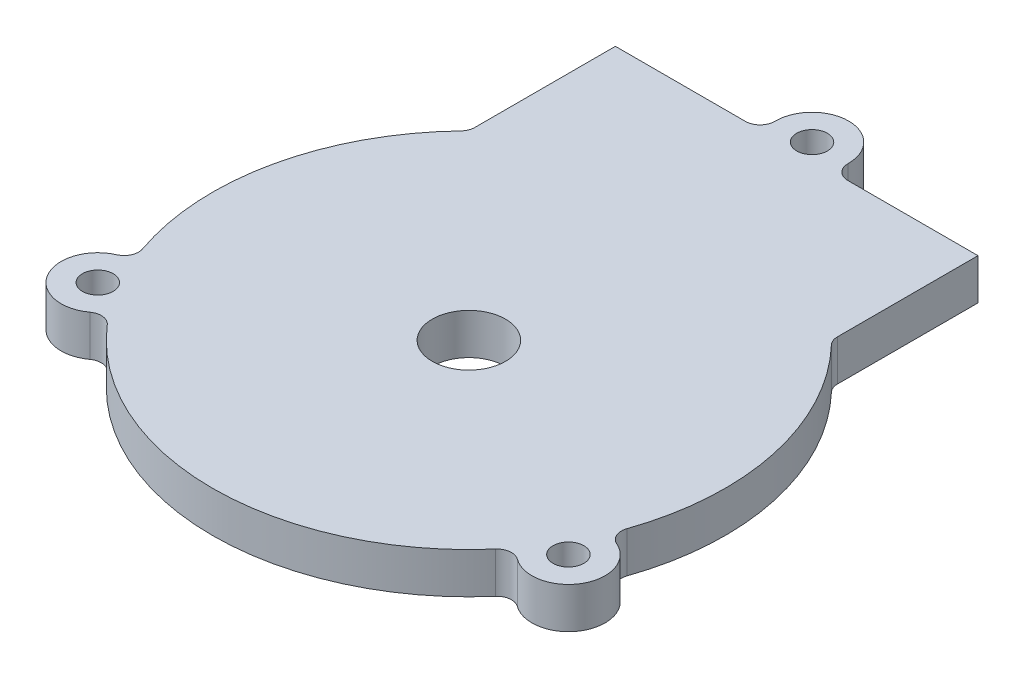
SolidWorks part; units mm, degrees
ref_plane "Front Plane" through (0, 0, 0) normal (0, 0, 1) x (1, 0, 0)
ref_plane "Top Plane" through (0, 0, 0) normal (0, 1, 0) x (1, 0, 0)
ref_plane "Right Plane" through (0, 0, 0) normal (1, 0, 0) x (0, 0, -1)
sketch "Sketch13" plane through (0, 0, 0) normal (0, 1, 0) x (1, 0, 0)
  circle A0 centre (0, 0) radius 35
extrude "Boss-Extrude3" add sketch "Sketch13" along normal blind 5.588
sketch "Sketch14" plane through (0, 5.588, 0) normal (0, 1, 0) x (1, 0, 0)
  line L0 (-24.7478, 24.7497) -> (24.7477, 24.7498)
  line L1 (-24.7478, 24.7497) -> (-24.7479, 44.7452)
  line L2 (24.7477, 24.7498) -> (24.7476, 44.7454)
  line L3 (-24.7479, 44.7452) -> (24.7476, 44.7454)
  line L4 (0, 0) -> (60.4611, -34.8658) construction
  line L5 (0, 0) -> (-56.6044, -32.6614) construction
  line L7 (-3.939, 44.1714) -> (-8.8985, 44.1714)
  line L8 (-3.939, 44.1714) -> (-3.939, 47.547)
  line L9 (-3.939, 47.547) -> (-8.8985, 47.547)
  line L10 (-8.8985, 44.1714) -> (-8.8985, 47.547)
  arc A0 (0, 35) -> (-24.7478, 24.7497) centre (0, 0) ccw construction
  circle A1 centre (0, 0) radius 35 construction
  arc A2 (0, 35) -> (-30.3109, -17.4999) centre (0, 0) ccw construction
  arc A3 (0, 35) -> (30.3118, -17.4984) centre (0, 0) ccw
  arc A4 (0, 35) -> (24.7477, 24.7498) centre (0, 0) ccw construction
  circle A5 centre (32.1365, -18.5413) radius 2.1017
  circle A6 centre (32.1365, -18.5413) radius 4.9951
  circle A7 centre (-32.1465, -18.5162) radius 2.0981
  circle A8 centre (-32.1465, -18.5162) radius 4.9995
extrude "Boss-Extrude4" add sketch "Sketch14" against normal up to surface (5.588 mm away) contours L0 L1 L3 L2 up to face at (0, 0, 35)
sketch "Sketch15" plane through (0, 5.588, 0) normal (0, 1, 0) x (1, 0, 0)
  line L0 (0, 0) -> (0, 62.3966) construction
  line L1 (-0.0001, 44.7453) -> (0, 46.8414) construction
  line L2 (-24.7479, 44.7452) -> (24.7476, 44.7454) construction
  circle A0 centre (0, 46.8414) radius 2.0961
  circle A1 centre (0, 46.8414) radius 4.996
extrude "Boss-Extrude11" add sketch "Sketch15" against normal blind 5.588 contours A1 | A0
extrude "Boss-Extrude12" add sketch "Sketch14<6>" against normal up to surface (5.588 mm away) contours A6 up to face at (0, 0, -29.3038)
sketch "Sketch14<6>" plane through (0, 5.588, 0) normal (0, 1, 0) x (1, 0, 0) same geometry as "Sketch14"
extrude "Boss-Extrude14" add sketch "Sketch14<8>" against normal through all contours L0 A5 region at (32.1365, 5.588, 18.5413)
sketch "Sketch14<8>" plane through (0, 5.588, 0) normal (0, 1, 0) x (1, 0, 0) same geometry as "Sketch14"
hole_wizard "Ø4.2 (4.2) Diameter Hole1" positions "Sketch22" profile "Sketch23" hole size "Ø4.2" standard "ANSI Metric" end condition through all
sketch "Sketch22" plane through (0, 5.588, 0) normal (0, 1, 0) x (1, 0, 0)
  point P0 (32.1248, -18.5356)
sketch "Sketch23" plane through (32.1248, 5.588, 18.5356) normal (1, 0, 0) x (0, 0, 1)
  line L0 (0, 0) -> (0, 5.588)
  line L1 (0, 5.588) -> (2.1, 5.588)
  line L2 (2.1, 5.588) -> (2.1, 0)
  line L5 (2.1, 0) -> (0, 0)
  line L11 (0, -6.35) -> (0, 107.95) construction
  dimension "Thru Hole Dia." = 4.2
  dimension "Thru Hole Depth" = 5.588
extrude "Boss-Extrude15" add sketch "Sketch14<11>" against normal up to surface (5.588 mm away) contours A8 up to face at (32.1248, 0, 20.6356)
sketch "Sketch14<11>" plane through (0, 5.588, 0) normal (0, 1, 0) x (1, 0, 0) same geometry as "Sketch14"
hole_wizard "Ø4.2 (4.2) Diameter Hole2" positions "Sketch26" profile "Sketch27" hole size "Ø4.2" standard "ANSI Metric" end condition through all
sketch "Sketch26" plane through (0, 5.588, 0) normal (0, 1, 0) x (1, 0, 0)
  point P0 (-32.148, -18.5088)
  point P2 (-32.148, -18.5088)
sketch "Sketch27" plane through (-32.148, 5.588, 18.5088) normal (1, 0, 0) x (0, 0, 1)
  line L0 (0, 0) -> (0, 5.588)
  line L1 (0, 5.588) -> (2.1, 5.588)
  line L2 (2.1, 5.588) -> (2.1, 0)
  line L5 (2.1, 0) -> (0, 0)
  line L11 (0, -6.35) -> (0, 107.95) construction
  dimension "Thru Hole Dia." = 4.2
  dimension "Thru Hole Depth" = 5.588
fillet "Fillet4" radius 2 1 edges at (-24.7478, 2.794, -24.7497)
fillet "Fillet6" radius 2 1 edges at (-32.2839, 2.794, 13.5185)
fillet "Fillet7" radius 2 1 edges at (-27.8924, 2.794, 21.1427)
fillet "Fillet8" radius 2 1 edges at (27.8812, 2.794, 21.1574)
fillet "Fillet9" radius 2 1 edges at (32.2715, 2.794, 13.548)
fillet "Fillet10" radius 2 1 edges at (24.7477, 2.794, -24.7498)
fillet "Fillet11" radius 2 1 edges at (4.535, 2.794, -44.7453)
fillet "Fillet12" radius 2 1 edges at (-4.535, 2.794, -44.7453)
sketch "Sketch28" plane through (0, 5.588, 0) normal (0, 1, 0) x (1, 0, 0)
  circle A0 centre (0, 0) radius 5
extrude "Cut-Extrude1" cut sketch "Sketch28" against normal up to surface (5.588 mm away) up to face at (-32.148, 0, 20.6088)
